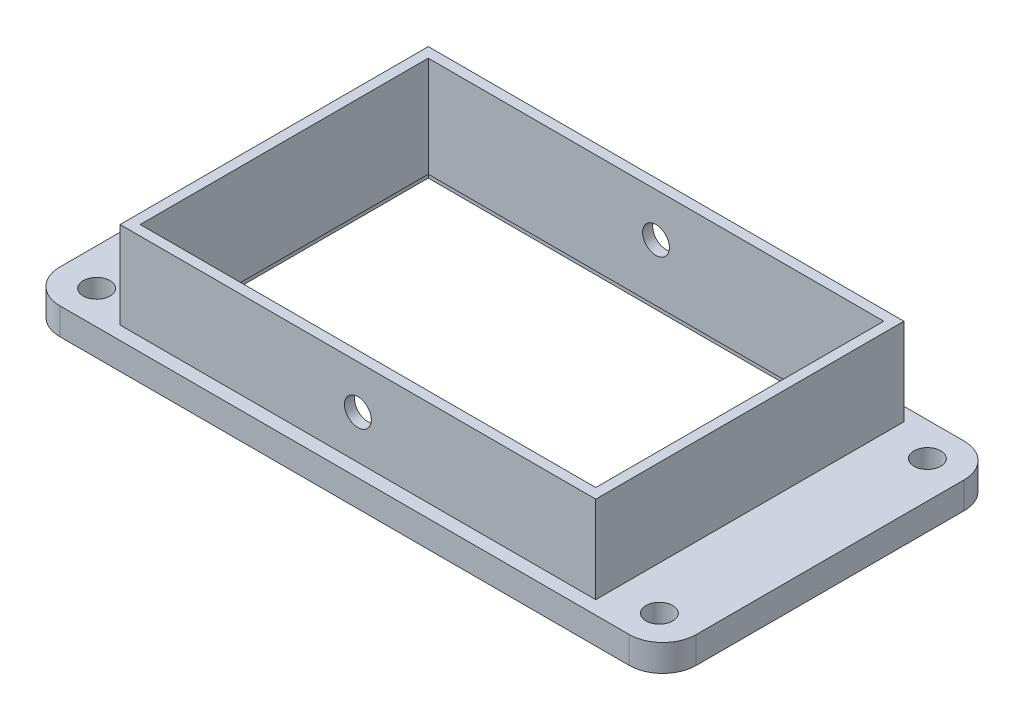
SolidWorks part; units mm, degrees
ref_plane "前视基准面" through (0, 0, 0) normal (0, 0, 1) x (1, 0, 0)
ref_plane "上视基准面" through (0, 0, 0) normal (0, 1, 0) x (1, 0, 0)
ref_plane "右视基准面" through (0, 0, 0) normal (1, 0, 0) x (0, 0, -1)
sketch "草图1" plane through (0, 0, 0) normal (0, 1, 0) x (1, 0, 0)
  line L0 (-1.5, 44.5) -> (69.5, 44.5)
  line L1 (0, 0) -> (68, 0)
  line L2 (0, 0) -> (0, 43)
  line L3 (0, 43) -> (68, 43)
  line L4 (68, 0) -> (68, 43)
  line L5 (69.5, -1.5) -> (69.5, 44.5)
  line L6 (-1.5, -1.5) -> (69.5, -1.5)
  line L7 (-1.5, -1.5) -> (-1.5, 44.5)
  dimension "D1" = 68
  dimension "D2" = 43
  dimension "D3" = 1.5
extrude "凸台-拉伸1" add sketch "草图1" along normal blind 15
sketch "草图2" plane through (0, 0, 0) normal (0, -1, 0) x (1, 0, 0)
  line L0 (34, -44.5) -> (34, 16.7584) construction
  line L1 (69.5, -44.5) -> (-1.5, -44.5)
  line L2 (69.5, -44.5) -> (69.5, 1.5)
  line L3 (69.5, 1.5) -> (-1.5, 1.5)
  line L4 (-1.5, -44.5) -> (-1.5, 1.5)
  line L5 (76.5, -46.5) -> (-8.5, -46.5)
  line L6 (81.5, -41.5) -> (81.5, -1.5)
  line L7 (76.5, 3.5) -> (-8.5, 3.5)
  line L8 (-13.5, -41.5) -> (-13.5, -1.5)
  line L9 (68, -21.5) -> (-28.8068, -21.5) construction
  line L10 (68, 0) -> (68, -43) construction
  circle A0 centre (76, -41.5) radius 2
  circle A1 centre (76, -1.5) radius 2
  circle A2 centre (-8, -1.5) radius 2
  circle A3 centre (-8, -41.5) radius 2
  arc A4 (-8.5, -46.5) -> (-13.5, -41.5) centre (-8.5, -41.5) cw
  arc A5 (-8.5, 3.5) -> (-13.5, -1.5) centre (-8.5, -1.5) ccw
  arc A6 (81.5, -1.5) -> (76.5, 3.5) centre (76.5, -1.5) ccw
  arc A7 (76.5, -46.5) -> (81.5, -41.5) centre (76.5, -41.5) ccw
  dimension "D5" = 4
  dimension "D8" = 5
  dimension "D1" = 12
  dimension "D2" = 12
  dimension "D3" = 2
  dimension "D4" = 2
  dimension "D6" = 42
  dimension "D7" = 20
extrude "凸台-拉伸2" add sketch "草图2" against normal blind 2
extrude "凸台-拉伸3" add sketch "草图2<2>" along normal blind 2
sketch "草图2<2>" plane through (0, 0, 0) normal (0, -1, 0) x (1, 0, 0) same geometry as "草图2"
sketch "草图3" plane through (0, 0, 1.5) normal (0, 0, 1) x (1, 0, 0)
  line L0 (34, 15) -> (34, 2) construction
  line L1 (-1.5, 15) -> (69.5, 15) construction
  line L2 (69.5, 2) -> (-1.5, 2) construction
  circle A0 centre (34, 8.5) radius 2
  dimension "D1" = 4
extrude "切除-拉伸1" cut sketch "草图3" against normal through all
